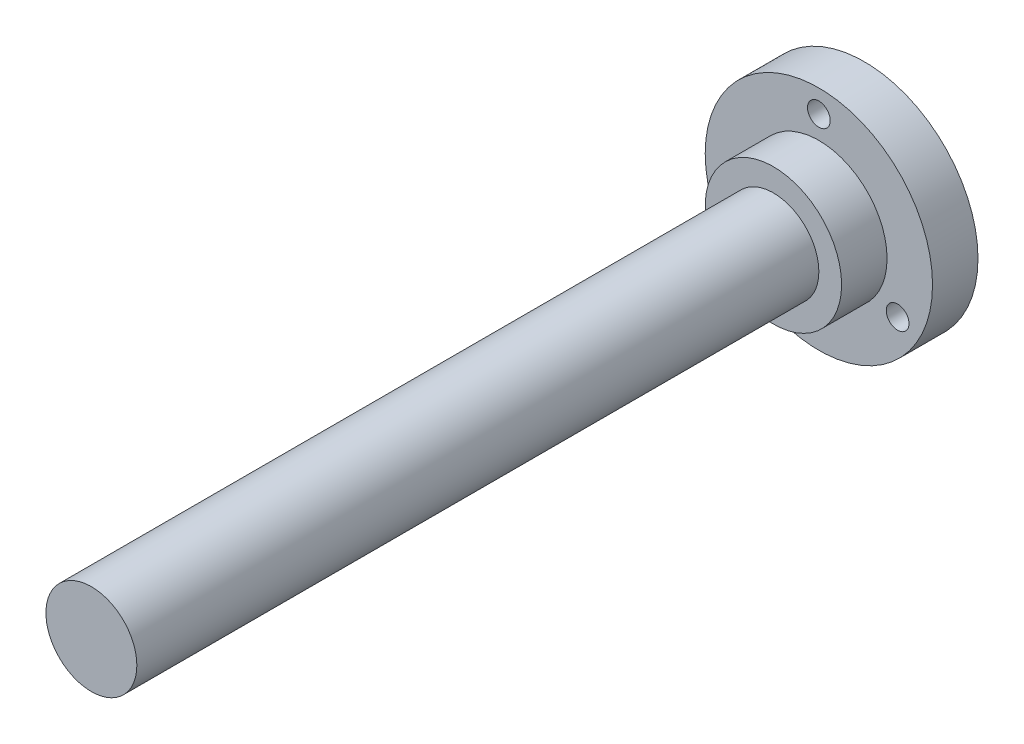
SolidWorks part; units mm, degrees
ref_plane "Front Plane" through (0, 0, 0) normal (0, 0, 1) x (1, 0, 0)
ref_plane "Top Plane" through (0, 0, 0) normal (0, 1, 0) x (1, 0, 0)
ref_plane "Right Plane" through (0, 0, 0) normal (1, 0, 0) x (0, 0, -1)
sketch "Sketch1" plane through (0, 0, 0) normal (0, 0, 1) x (1, 0, 0)
  circle A0 centre (0, 0) radius 25
  circle A1 centre (0, 20) radius 2.5
  circle A2 centre (17.3205, -10) radius 2.5
  circle A3 centre (-17.3205, -10) radius 2.5
  dimension "D1" = 50
  dimension "D2" = 5
  dimension "D4" = 20
  dimension "D3" = 3
extrude "Boss-Extrude1" add sketch "Sketch1" along normal blind 10
sketch "Sketch2" plane through (0, 0, 10) normal (0, 0, 1) x (1, 0, 0)
  circle A0 centre (0, 0) radius 15
  dimension "D1" = 30
extrude "Boss-Extrude2" add sketch "Sketch2" along normal blind 10
sketch "Sketch3" plane through (0, 0, 20) normal (0, 0, 1) x (1, 0, 0)
  circle A0 centre (0, 0) radius 10
  dimension "D1" = 20
extrude "Boss-Extrude3" add sketch "Sketch3" along normal blind 150
